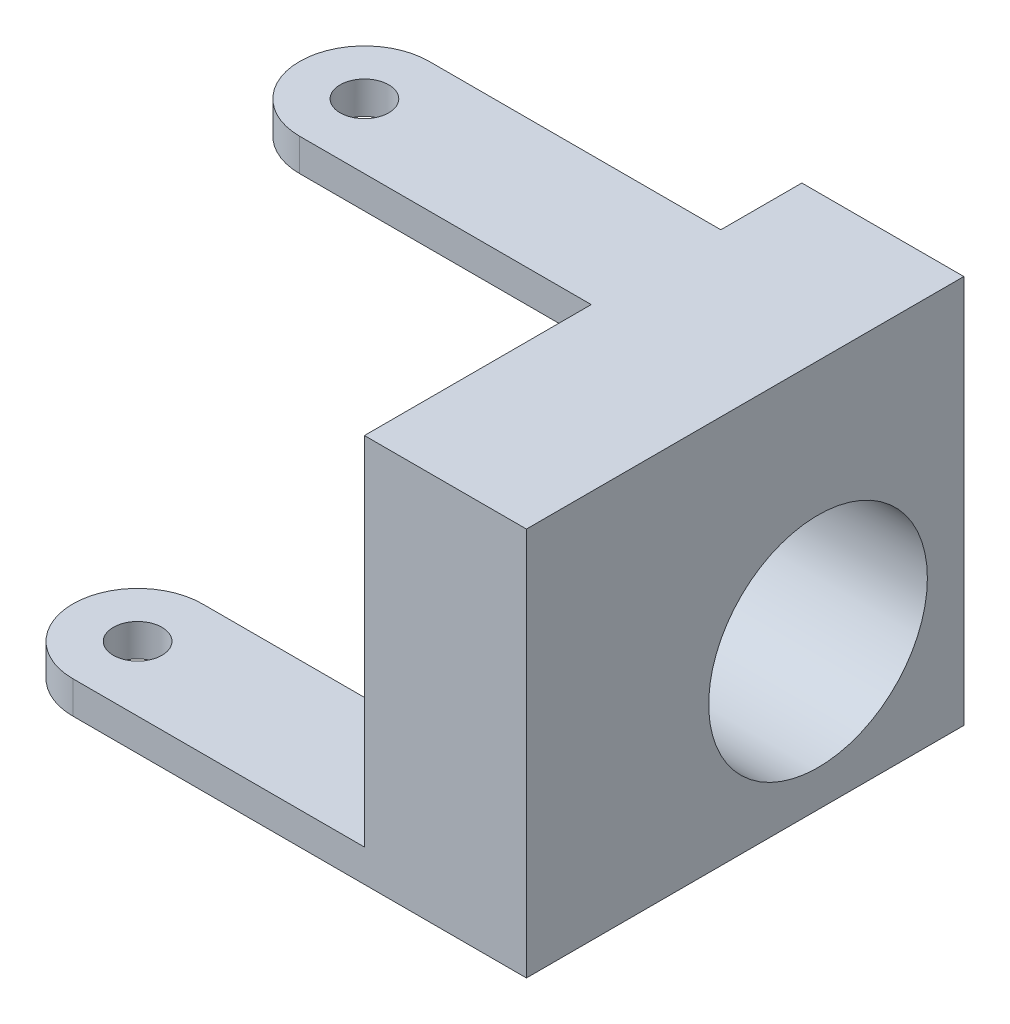
SolidWorks part; units mm, degrees
ref_plane "Front Plane" through (0, 0, 0) normal (0, 0, 1) x (1, 0, 0)
ref_plane "Top Plane" through (0, 0, 0) normal (0, 1, 0) x (1, 0, 0)
ref_plane "Right Plane" through (0, 0, 0) normal (1, 0, 0) x (0, 0, -1)
sketch "Sketch2" plane through (0, 0, 0) normal (0, 1, 0) x (1, 0, 0)
  line L0 (-5, -4.5) -> (5, -4.5) construction
  line L1 (-5, -18) -> (5, -18)
  line L2 (-5, -18) -> (-5, 9)
  line L3 (-5, 9) -> (5, 9)
  line L4 (5, -18) -> (5, 9)
  line L5 (0, 9) -> (0, -18) construction
  point P0 (0, 0)
  dimension "D3" = 9
  dimension "D1" = 10
  dimension "D2" = 18
extrude "Boss-Extrude1" add sketch "Sketch2" along normal blind 24
sketch "Sketch3" plane through (5, 0, 0) normal (1, 0, 0) x (0, 0, -1)
  line L0 (-18, 9) -> (9, 9) construction
  line L4 (-18, 0) -> (9, 0) construction
  line L6 (-18, 24) -> (-18, 0) construction
  line L7 (9, 24) -> (9, 0) construction
  circle A0 centre (0, 9) radius 6.75
  point P7 (-18.9975, 8)
  dimension "D1" = 13.5
  dimension "D2" = 9
extrude "Cut-Extrude1" cut sketch "Sketch3" against normal up to surface (10 mm away) up to face at (-5, 12, 4.5)
sketch "Sketch6" plane through (5, 0, 0) normal (1, 0, 0) x (0, 0, -1)
  line L0 (-18, 24) -> (9, 24) construction
  line L1 (-4, 24) -> (4, 24)
  line L2 (-4, 24) -> (-4, 22)
  line L3 (-4, 22) -> (4, 22)
  line L4 (4, 24) -> (4, 22)
  line L5 (0, 24) -> (0, 0) construction
  dimension "D1" = 8
  dimension "D2" = 2
extrude "Boss-Extrude2" add sketch "Sketch6" against normal blind 32
fillet "Fillet1" 2 edges at (-27, 23, 4) (-27, 23, -4) type full round first side face at (-16, 23, 4) second side face at (-16, 23, -4) middle face at (-27, 23, 0)
sketch "Sketch8" plane through (0, 24, 0) normal (0, 1, 0) x (1, 0, 0)
  circle A0 centre (-23, 0) radius 1.5
  dimension "D1" = 3
extrude "Cut-Extrude2" cut sketch "Sketch8" against normal up to surface (2 mm away) up to face at (-15, 22, 0)
sketch "Sketch10" plane through (-5, 0, 0) normal (-1, 0, 0) x (0, 0, 1)
  line L1 (18, 0) -> (10, 0)
  line L2 (18, 0) -> (18, 2)
  line L3 (18, 2) -> (10, 2)
  line L4 (10, 0) -> (10, 2)
  dimension "D1" = 8
  dimension "D2" = 2
extrude "Boss-Extrude3" add sketch "Sketch10" along normal blind 22
fillet "Fillet2" 2 edges at (-27, 1, 18) (-27, 1, 10) type full round first side face at (-9, 8.6667, 18) second side face at (-16, 1, 10) middle face at (-27, 1, 14)
sketch "Sketch11" plane through (0, 2, 0) normal (0, 1, 0) x (1, 0, 0)
  circle A0 centre (-23, -14) radius 1.5
  dimension "D1" = 3
extrude "Cut-Extrude4" cut sketch "Sketch11" against normal up to surface (2 mm away) up to face at (-8.3333, 0, 6.3333)
